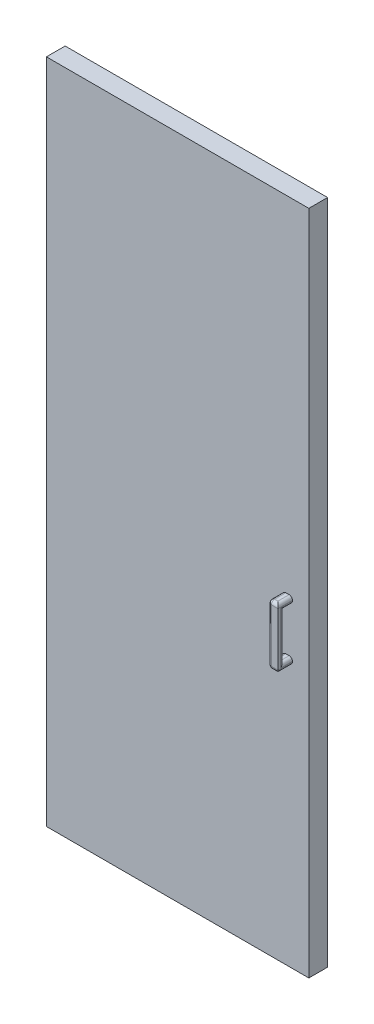
SolidWorks part; units mm, degrees
ref_plane "Front Plane" through (0, 0, 0) normal (0, 0, 1) x (1, 0, 0)
ref_plane "Top Plane" through (0, 0, 0) normal (0, 1, 0) x (1, 0, 0)
ref_plane "Right Plane" through (0, 0, 0) normal (1, 0, 0) x (0, 0, -1)
sketch "Sketch1" plane through (0, 0, 0) normal (0, 0, 1) x (1, 0, 0)
  line L0 (0, 0) -> (0, 18.7953) construction
  line L1 (0, 0) -> (0, 446.2018)
  line L2 (0, 446.2018) -> (-800, 446.2018)
  line L3 (-800, 446.2018) -> (-800, -1585.7982)
  line L4 (-800, -1585.7982) -> (0, -1585.7982)
  line L5 (0, -1585.7982) -> (0, 0)
  line L7 (-203.7641, -553.7982) -> (-173.7641, -553.7982)
  line L8 (-203.7641, -553.7982) -> (-203.7641, -735.7982)
  line L9 (-203.7641, -735.7982) -> (-173.7641, -735.7982)
  line L10 (-173.7641, -553.7982) -> (-173.7641, -735.7982)
  line L11 (-203.7641, -553.7982) -> (-173.7641, -735.7982) construction
  line L12 (-203.7641, -735.7982) -> (-173.7641, -553.7982) construction
  point P9 (-188.7641, -644.7982)
  dimension "D1" = 800
  dimension "D2" = 2032
  dimension "D3" = 30
  dimension "D4" = 182
  dimension "D5" = 850
extrude "Boss-Extrude2" add sketch "Sketch1" along normal blind 57.15 contours L3 L4 L5 L1 L2
sketch "Sketch4" plane through (0, 0, 57.15) normal (0, 0, 1) x (1, 0, 0)
  line L0 (-50, 0) -> (-50, -1857.8255) construction
  line L1 (-800, -1585.7982) -> (0, -1585.7982) construction
  line L2 (-80, -603.7982) -> (-50, -603.7982)
  line L3 (-80, -603.7982) -> (-80, -785.7982)
  line L4 (-80, -785.7982) -> (-50, -785.7982)
  line L5 (-50, -603.7982) -> (-50, -785.7982)
  line L6 (-80, -603.7982) -> (-50, -785.7982) construction
  line L7 (-80, -785.7982) -> (-50, -603.7982) construction
  point P1 (-65, -694.7982)
  dimension "D1" = 50
  dimension "D2" = 30
  dimension "D3" = 182
  dimension "D4" = 800
extrude "Boss-Extrude3" add sketch "Sketch4" along normal blind 44
sketch "Sketch5" plane through (-80, 0, 0) normal (-1, 0, 0) x (0, 0, 1)
  line L0 (57.15, -603.7982) -> (57.15, -785.7982)
  line L1 (57.15, -624.7982) -> (83.15, -624.7982)
  line L2 (83.15, -624.7982) -> (83.15, -764.7982)
  line L3 (83.15, -764.7982) -> (57.15, -764.7982)
  line L4 (57.15, -624.7982) -> (57.15, -764.7982)
  line L5 (101.15, -785.7982) -> (57.15, -785.7982) construction
  dimension "D1" = 140
  dimension "D2" = 21
  dimension "D3" = 26
extrude "Cut-Extrude1" cut sketch "Sketch5" against normal blind 44 contours L3 L2 L1 L0 region at (-80, -694.7982, 70.15)
fillet "Fillet1" radius 10 13 edges at (-80, -694.7982, 83.15) (-80, -603.7982, 79.15) (-80, -624.7982, 70.15) (-50, -603.7982, 79.15) (-50, -624.7982, 70.15) (-50, -694.7982, 83.15) (-50, -764.7982, 70.15) (-50, -785.7982, 79.15) (-80, -785.7982, 79.15) (-80, -764.7982, 70.15) (-80, -694.7982, 101.15) (-65, -785.7982, 101.15) (-65, -603.7982, 101.15)
sketch "Sketch6" plane through (0, 0, 0) normal (0, 0, -1) x (-1, 0, 0)
  line L0 (800, -1585.7982) -> (0, -1585.7982) construction
  line L1 (25, -924.7982) -> (145, -924.7982)
  line L2 (25, -924.7982) -> (25, -464.7982)
  line L3 (25, -464.7982) -> (145, -464.7982)
  line L4 (145, -924.7982) -> (145, -464.7982)
  line L5 (25, -924.7982) -> (145, -464.7982) construction
  line L6 (25, -464.7982) -> (145, -924.7982) construction
  line L7 (0, -1585.7982) -> (0, 446.2018) construction
  point P0 (85, -694.7982)
  dimension "D1" = 120
  dimension "D2" = 891
  dimension "D3" = 460
  dimension "D4" = 25
extrude "Boss-Extrude4" add sketch "Sketch6" along normal blind 10
